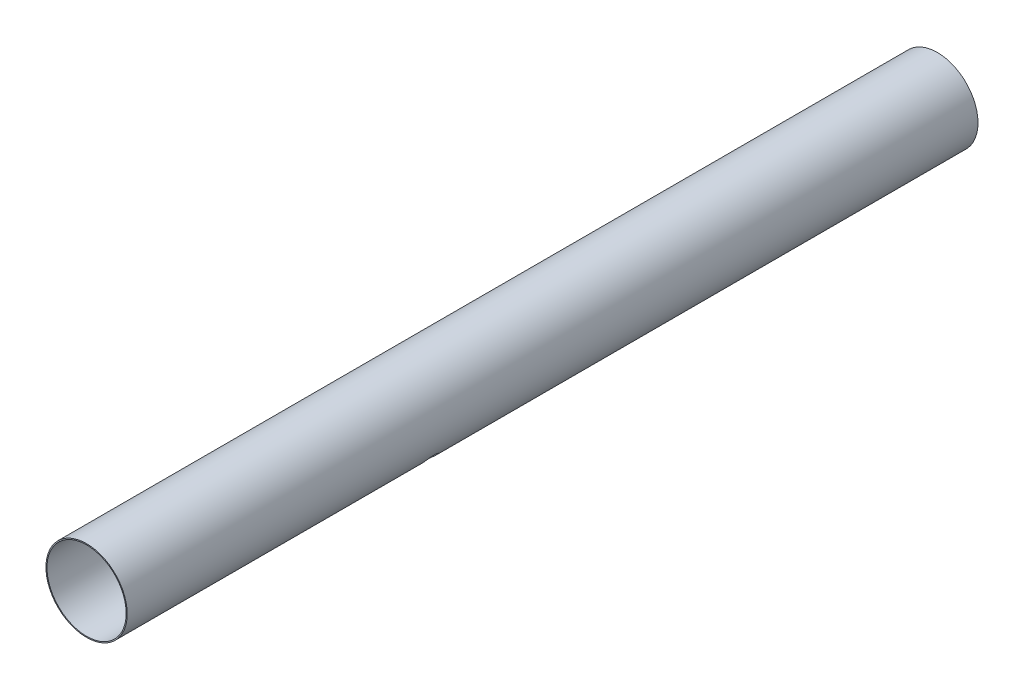
SolidWorks part; units mm, degrees
material "E-Glass Fiber"
ref_plane "Front" through (0, 0, 0) normal (0, 0, 1) x (1, 0, 0)
ref_plane "Top" through (0, 0, 0) normal (0, 1, 0) x (1, 0, 0)
ref_plane "Right" through (0, 0, 0) normal (1, 0, 0) x (0, 0, -1)
sketch "Sketch1" plane through (0, 0, 0) normal (0, 0, 1) x (1, 0, 0)
  circle A0 centre (0, 0) radius 78.35
  circle A1 centre (0, 0) radius 76.35
  dimension "D1" = 2
  dimension "D2" = 152.7
extrude "Boss-Extrude1" add sketch "Sketch1" along normal blind 1640
sketch "Sketch4" plane through (0, 0, 0) normal (0, 0, 1) x (1, 0, 0)
  line L0 (0, 0) -> (25.0476, -25.0476) construction
  line L1 (0, 0) -> (0, -24.8691) construction
  dimension "D1" = 45
ref_plane "Plane1" through (0, 0, 0) normal (0.7071, -0.7071, 0) x (0, 0, -1)
sketch "Sketch5" plane through (0, 0, 0) normal (0.7071, -0.7071, 0) x (0, 0, -1)
  line L0 (0, -78.35) -> (0, 78.35) construction
  circle A0 centre (-1034.89, 0) radius 15
  dimension "D1" = 30
  dimension "D2" = 1034.89
extrude "Cut-Extrude2" cut sketch "Sketch5" along normal through all
